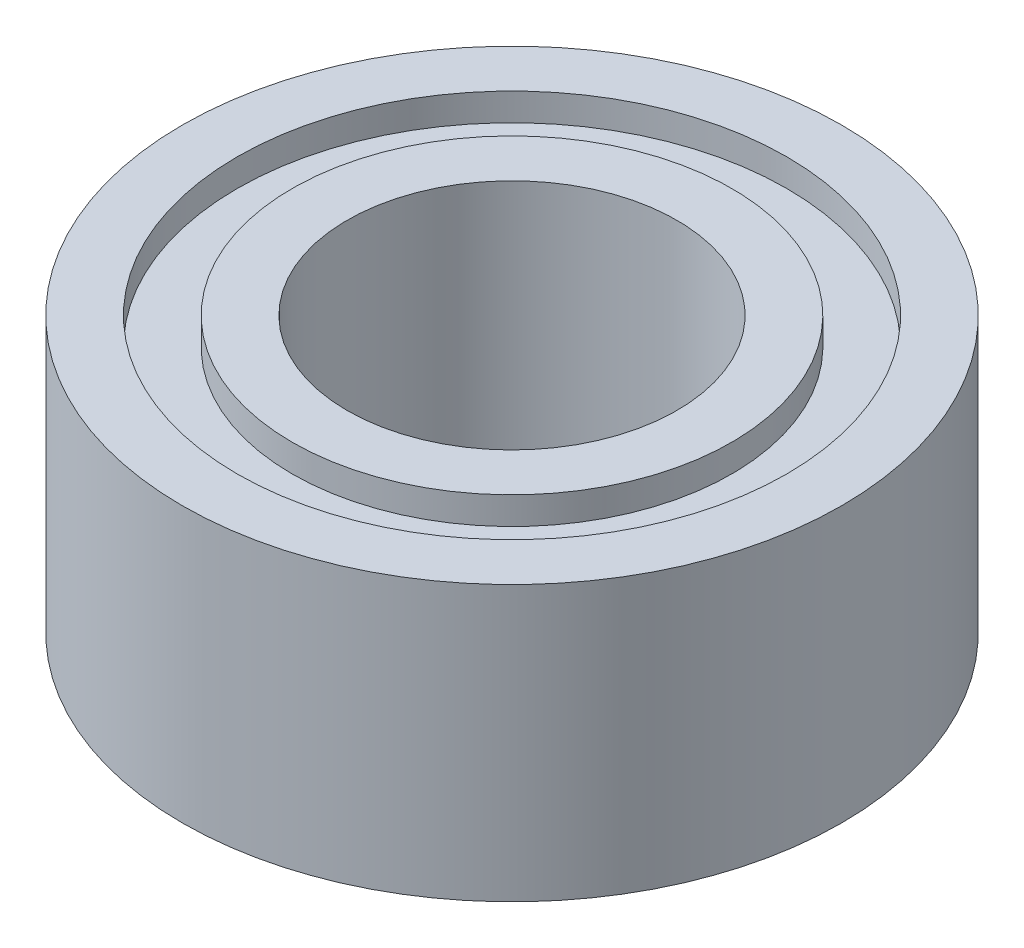
SolidWorks part; units mm, degrees
ref_plane "前视基准面" through (0, 0, 0) normal (0, 0, 1) x (1, 0, 0)
ref_plane "上视基准面" through (0, 0, 0) normal (0, 1, 0) x (1, 0, 0)
ref_plane "右视基准面" through (0, 0, 0) normal (1, 0, 0) x (0, 0, -1)
other "Configuration Table"
sketch "草图1" plane through (0, 0, 0) normal (0, 1, 0) x (1, 0, 0)
  circle A0 centre (0, 0) radius 1.5
  circle A1 centre (0, 0) radius 2
  dimension "D1" = 3
  dimension "D2" = 4
extrude "凸台-拉伸1" add sketch "草图1" along normal blind 1.25 and the other way blind 1.25
sketch "草图2" plane through (0, 0, 0) normal (0, 1, 0) x (1, 0, 0)
  circle A0 centre (0, 0) radius 2
  circle A1 centre (0, 0) radius 2.5
  dimension "D1" = 5
  dimension "D2" = 4
extrude "凸台-拉伸2" add sketch "草图2" along normal blind 1 and the other way blind 1
sketch "草图3" plane through (0, 0, 0) normal (0, 1, 0) x (1, 0, 0)
  circle A0 centre (0, 0) radius 2.5
  circle A1 centre (0, 0) radius 3
  dimension "D1" = 6
  dimension "D2" = 5
extrude "凸台-拉伸3" add sketch "草图3" along normal blind 1.25 and the other way blind 1.25
